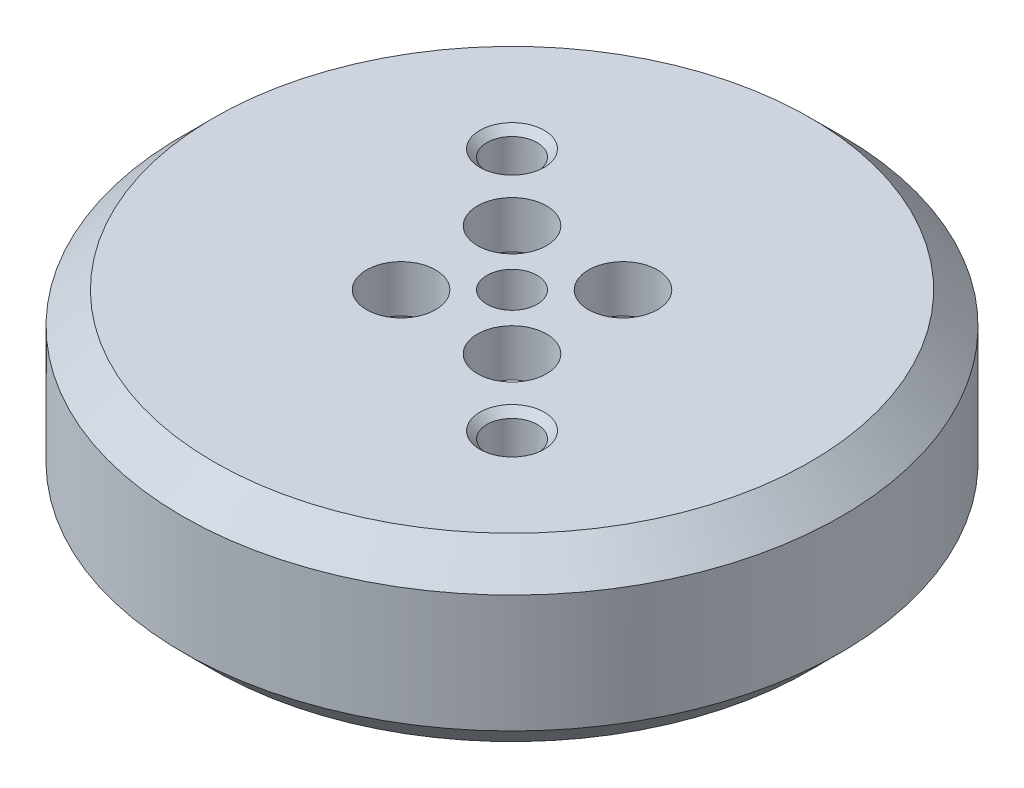
SolidWorks part; units mm, degrees
ref_plane "Front Plane" through (0, 0, 0) normal (0, 0, 1) x (1, 0, 0)
ref_plane "Top Plane" through (0, 0, 0) normal (0, 1, 0) x (1, 0, 0)
ref_plane "Right Plane" through (0, 0, 0) normal (1, 0, 0) x (0, 0, -1)
sketch "Sketch1" plane through (0, 0, 0) normal (0, 1, 0) x (1, 0, 0)
  circle A0 centre (0, 0) radius 10.5
  dimension "D1" = 21
extrude "Boss-Extrude1" add sketch "Sketch1" along normal blind 1.5
sketch "Sketch2" plane through (0, 1.5, 0) normal (0, 1, 0) x (1, 0, 0)
  circle A0 centre (0, 0) radius 0.8
  dimension "D1" = 1.6
extrude "Cut-Extrude1" cut sketch "Sketch2" against normal through all both and the other way through all
hole_wizard "M2 Clearance Hole1" positions "Sketch3" profile "Sketch4" hole size "M2" standard "ANSI Metric"
sketch "Sketch3" plane through (0, 1.5, 0) normal (0, 1, 0) x (1, 0, 0)
  line L1 (-1.7678, 1.7678) -> (1.7678, 1.7678)
  line L2 (-1.7678, 1.7678) -> (-1.7678, -1.7678)
  line L3 (-1.7678, -1.7678) -> (1.7678, -1.7678)
  line L4 (1.7678, 1.7678) -> (1.7678, -1.7678)
  line L5 (-1.7678, 1.7678) -> (1.7678, -1.7678) construction
  point P0 (-1.7678, 1.7678)
  point P2 (1.7678, 1.7678)
  point P4 (1.7678, -1.7678)
  point P6 (-1.7678, -1.7678)
  point P120 (0, 0)
  dimension "D1" = 5
sketch "Sketch4" plane through (-1.7678, 1.5, -1.7678) normal (1, 0, 0) x (0, 0, 1)
  line L0 (0, 0) -> (0, 5.6609)
  line L1 (0, 5.6609) -> (1.1, 5)
  line L2 (1.1, 5) -> (1.1, 0)
  line L5 (1.1, 0) -> (0, 0)
  line L10 (0, 5.6609) -> (-1.1, 5) construction
  line L11 (0, -6.35) -> (0, 107.95) construction
  dimension "Hole Dia." = 2.2
  dimension "Hole Depth" = 5
  dimension "Drill Angle" = 118
sketch "Sketch6" plane through (0, 0, 0) normal (0, 0, 1) x (1, 0, 0)
  line L0 (-10.5, 0) -> (-10.5, -1.25)
  line L1 (-10.5, -1.25) -> (-7.2, -1.25)
  line L2 (-7.2, -1.25) -> (-5, 0)
  line L3 (-5, 0) -> (-10.5, 0)
  line L4 (0, 0) -> (0, -5.6432) construction
  dimension "D1" = 1.25
  dimension "D2" = 5
  dimension "D3" = 7.2
revolve "Revolve1" add sketch "Sketch6" angle 360 about L4
sketch "Sketch7" plane through (0, -1.25, 0) normal (0, -1, 0) x (1, 0, 0)
  circle A0 centre (0, 0) radius 7.2 construction
  circle A1 centre (0, 0) radius 10.5
  circle A2 centre (0, 0) radius 10.5
  circle A3 centre (0, 0) radius 7.2
  dimension "D1" = 0
extrude "Boss-Extrude2" add sketch "Sketch7" along normal blind 3
fillet "Fillet1" radius 1 2 edges at (0, 0, 5) (0, -1.25, 7.2)
chamfer "Chamfer1" distance 1 angle 45 1 edges at (0, 1.5, 10.5)
chamfer "Chamfer2" distance 1 angle 45 1 edges at (0, -4.25, -10.5)
hole_wizard "M2x0.4 Tapped Hole1" positions "Sketch8" profile "Sketch9" tap size "M2x0.4" standard "ANSI Metric"
sketch "Sketch8" plane through (0, 1.5, 0) normal (0, 1, 0) x (1, 0, 0)
  line L0 (-3.8891, 3.8891) -> (3.8891, -3.8891) construction
  circle A1 centre (-1.7678, 1.7678) radius 1.1 construction
  point P0 (-3.8891, 3.8891)
  point P2 (3.8891, -3.8891)
  point P12 (-1.7678, 1.7678)
  dimension "D1" = 11
sketch "Sketch9" plane through (-3.8891, 1.5, -3.8891) normal (1, 0, 0) x (0, 0, 1)
  line L0 (0, 0) -> (0, 5.6807)
  line L1 (0, 5.6807) -> (0.8, 5.2)
  line L2 (0.8, 5.2) -> (0.8, 0.225)
  line L3 (0.8, 0.225) -> (1.025, 0)
  line L5 (1.025, 0) -> (0, 0)
  line L6 (-0.8, 0.225) -> (-1.025, 0) construction
  line L10 (0, 5.6807) -> (-0.8, 5.2) construction
  line L11 (0, -6.35) -> (0, 107.95) construction
  dimension "Tap Drill Dia." = 1.6
  dimension "Tap Drill Depth" = 5.2
  dimension "Near C'Sink Dia." = 2.05
  dimension "Near C'Sink Angle" = 90
  dimension "Drill Angle" = 118
cosmetic thread "Hole Thread1"
cosmetic thread "Hole Thread2"
